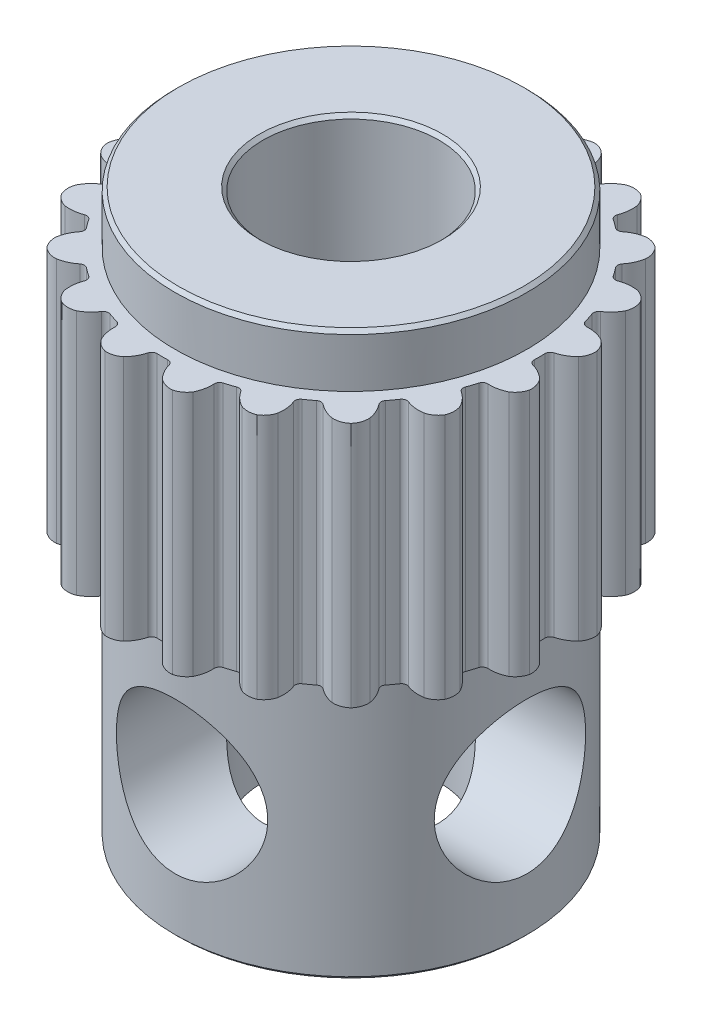
SolidWorks part; units mm, degrees
material "6061-T6 (SS)"
ref_plane "Front Plane" through (0, 0, 0) normal (0, 0, 1) x (1, 0, 0)
ref_plane "Top Plane" through (0, 0, 0) normal (0, 1, 0) x (1, 0, 0)
ref_plane "Right Plane" through (0, 0, 0) normal (1, 0, 0) x (0, 0, -1)
sketch "BodyS" plane through (0, 0, 0) normal (0, 0, 1) x (1, 0, 0)
  line L0 (6.11, -3.5) -> (6.11, 3.5)
  line L3 (6.11, 3.5) -> (2.5, 3.5)
  line L4 (2.5, 3.5) -> (2.5, -3.5)
  line L9 (2.5, -3.5) -> (6.11, -3.5)
  line L12 (0, 0) -> (6.11, 0) construction
  line L13 (0, 3.5) -> (0, -3.5) construction
  dimension "BoreDia" = 5
  dimension "Height" = 7
  dimension "BeltPathDiaControl" = 3.61
  dimension "RefBeltPathDia" = 12.22
revolve "Body" add sketch "BodyS" angle 360 about L13
sketch "GT2ProfileS" plane through (0, 0, 0) normal (0, 1, 0) x (1, 0, 0)
  line L1 (0, -6.11) -> (0, -5.36) construction
  line L2 (-0.9955, -6.0283) -> (-0.8733, -5.2884) construction
  line L3 (0, 0) -> (-0.8733, -5.2884) construction
  line L4 (0.9955, -6.0283) -> (0, 0) construction
  arc A3 (0.2997, -5.4688) -> (0.1507, -5.3579) centre (0.1549, -5.5078) ccw
  arc A4 (-0.9955, -6.0283) -> (0.9955, -6.0283) centre (0, 0) ccw
  arc A5 (-0.2997, -5.4688) -> (-0.1507, -5.3579) centre (-0.1549, -5.5078) cw
  arc A6 (-0.2997, -5.4688) -> (-0.5497, -5.907) centre (-1.2653, -5.2085) cw
  arc A8 (-0.1507, -5.3579) -> (0.1507, -5.3579) centre (0, 0) ccw
  arc A9 (-0.5497, -5.907) -> (-0.9955, -6.0283) centre (-0.9051, -5.4808) cw
  arc A10 (0.2997, -5.4688) -> (0.5497, -5.907) centre (1.2653, -5.2085) ccw
  arc A11 (0.5497, -5.907) -> (0.9955, -6.0283) centre (0.9051, -5.4808) ccw
  circle A12 centre (0, 0) radius 5.36 construction
  circle A13 centre (0, 0) radius 6.11 construction
  dimension "BottomRadius" = 0.15
  dimension "MidRadius" = 1
  dimension "TopRadius" = 0.555
  dimension "Height" = 0.75
  dimension "XDistMidRadius" = 0.4
  dimension "ArcLengthAngle" = 18.755
  dimension "ArcLength" = 2
extrude "GT2Profile" cut sketch "GT2ProfileS" along direction (0, -1, 0) on the side against the normal up to next (3.5 mm away) and the other way up to next (3.5 mm away)
pattern_circular "GT2 Groove CP" count 20 over 360 about axis through (0, 3.5, 0) along (0, 1, 0) of "GT2Profile"
sketch "TopWallS" plane through (0, 3.5, 0) normal (0, 1, 0) x (1, 0, 0)
  circle A0 centre (0, 0) radius 2.5 construction
  circle A1 centre (0, 0) radius 2.5
  circle A2 centre (0, 0) radius 5
  dimension "Thickness" = 2.5
extrude "TopWall" add sketch "TopWallS" along normal blind 1.5
sketch "BottomWallS" plane through (0, -3.5, 0) normal (0, -1, 0) x (-1, 0, 0)
  circle A0 centre (0, 0) radius 2.5
  circle A1 centre (0, 0) radius 2.5 construction
  circle A2 centre (0, 0) radius 5
  circle A3 centre (0, 0) radius 5 construction
extrude "BottomWall" add sketch "BottomWallS" along normal blind 7.5
ref_plane "ClearanceHolePlane" through (0, 0, 5) normal (0, 0, 1) x (1, 0, 0)
hole_wizard " Clearance Hole1" positions "Sketch1" profile "Sketch2" hole size "M4" standard "ANSI Metric" end condition up to next
sketch "Sketch1" plane through (0, 0, 5) normal (0, 0, 1) x (1, 0, 0)
  line L0 (0, -11) -> (0, -3.5) construction
  line L1 (-5, -11) -> (5, -11) construction
  line L2 (-0.1507, -3.5) -> (0.1507, -3.5) construction
  point P0 (0, -7.25)
sketch "Sketch2" plane through (0, -7.25, 5) normal (1, 0, 0) x (0, -1, 0)
  line L0 (0, 0) -> (0, 2.5)
  line L1 (0, 2.5) -> (2.15, 2.5)
  line L2 (2.15, 2.5) -> (2.15, 0)
  line L5 (2.15, 0) -> (0, 0)
  line L11 (0, -6.35) -> (0, 107.95) construction
  dimension "Thru Hole Dia." = 4.3
  dimension "Thru Hole Depth" = 2.5
pattern_circular "CirPattern1" count 2 every 90 about axis through (0, -11, 0) along (0, 1, 0) of " Clearance Hole1"
chamfer "InnerC" distance 0.1 angle 45 2 edges at (0, 5, 2.5) (0, -11, -2.5)
chamfer "OuterC" distance 0.1 angle 45 2 edges at (0, -11, -5) (0, 5, 5)
equation "\"D1@GT2 Groove CP\"=int(360/\"ArcLengthAngle@GT2ProfileS\")+1"
